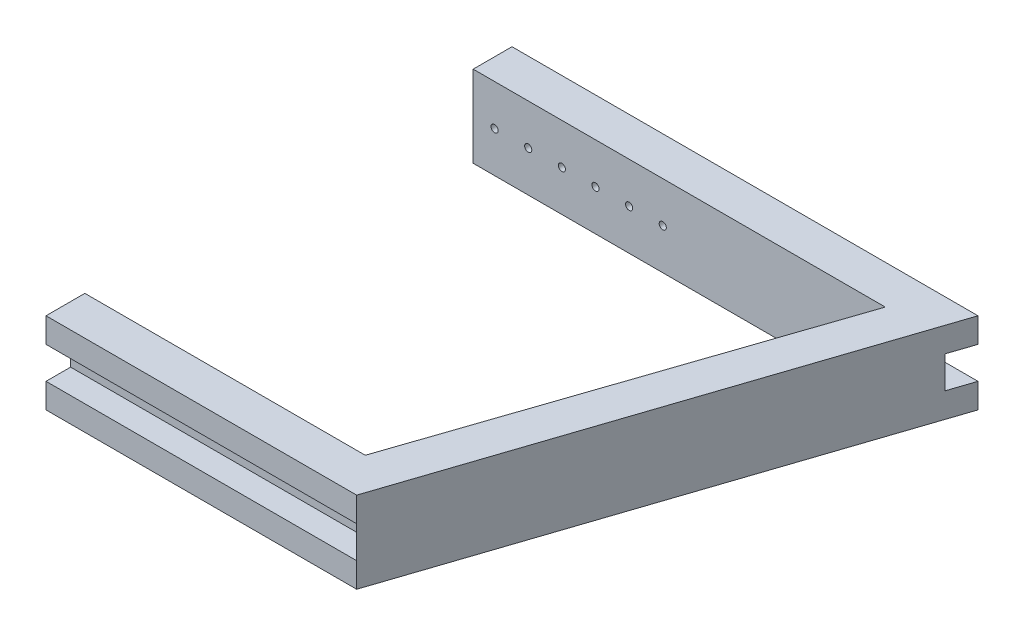
SolidWorks part; units mm, degrees
ref_plane "Front Plane" through (0, 0, 0) normal (0, 0, 1) x (1, 0, 0)
ref_plane "Top Plane" through (0, 0, 0) normal (0, 1, 0) x (1, 0, 0)
ref_plane "Right Plane" through (0, 0, 0) normal (1, 0, 0) x (0, 0, -1)
sketch "Sketch1" plane through (0, 0, 0) normal (0, 1, 0) x (1, 0, 0)
  line L0 (-228.6, 0) -> (228.6, 0)
  line L1 (-228.6, 0) -> (-228.6, -457.2) construction
  line L2 (-228.6, -457.2) -> (76.2, -457.2)
  line L3 (76.2, -457.2) -> (228.6, 0)
  line L4 (-228.6, 0) -> (-228.6, -38.1)
  line L5 (-228.6, -457.2) -> (-228.6, -419.1)
  line L6 (-228.6, -38.1) -> (399.2088, -38.1) construction
  line L7 (-228.6, -419.1) -> (435.0265, -419.1) construction
  line L8 (76.2, -457.2) -> (76.2, 0) construction
  line L9 (84.6667, -431.8) -> (46.5667, -419.1) construction
  line L10 (-228.6, -419.1) -> (46.5667, -419.1)
  line L11 (175.7391, -38.1) -> (46.5667, -419.1)
  line L12 (-228.6, -38.1) -> (175.7391, -38.1)
  line L13 (211.8839, -50.1483) -> (175.7391, -38.1) construction
  point P2 (0, 0)
  point P16 (46.5667, -419.1)
  dimension "D1" = 457.2
  dimension "D2" = 457.2
  dimension "D3" = 304.8
  dimension "D4" = 38.1
  dimension "D5" = 38.1
  dimension "D6" = 38.1
  dimension "D7" = 90
  dimension "D8" = 38.1
  dimension "D9" = 90
extrude "Boss-Extrude1" add sketch "Sketch1" along normal blind 80.0001
sketch "Sketch2" plane through (0, 0, 457.2) normal (0, 0, 1) x (1, 0, 0)
  line L0 (-228.6, 80.0001) -> (-228.6, 0) construction
  line L1 (-228.6, 55.6923) -> (76.2, 55.6923)
  line L2 (-228.6, 55.6923) -> (-228.6, 24.3078)
  line L3 (-228.6, 24.3078) -> (76.2, 24.3078)
  line L4 (76.2, 55.6923) -> (76.2, 24.3078)
  line L5 (76.2, 80.0001) -> (76.2, 0) construction
  point P8 (0, 0)
  point P9 (0, 0)
  point P11 (0, 0)
  point P13 (0, 0)
  dimension "D1" = 24.3078
  dimension "D2" = 24.3078
extrude "Cut-Extrude1" cut sketch "Sketch2" against normal blind 24.12
sketch "Sketch3" plane through (0, 0, 0) normal (0, 0, -1) x (-1, 0, 0)
  line L0 (-228.6, 80.0001) -> (-228.6, 0) construction
  line L1 (-228.6, 55.6923) -> (228.6, 55.6923)
  line L2 (-228.6, 55.6923) -> (-228.6, 24.3078)
  line L3 (-228.6, 24.3078) -> (228.6, 24.3078)
  line L4 (228.6, 55.6923) -> (228.6, 24.3078)
  line L5 (228.6, 80.0001) -> (228.6, 0) construction
  dimension "D1" = 24.3078
  dimension "D2" = 24.3078
extrude "Cut-Extrude2" cut sketch "Sketch3" against normal blind 24.12
sketch "Sketch4" plane through (0, 0, 433.08) normal (0, 0, 1) x (1, 0, 0)
  line L0 (-533.4, 40) -> (76.2, 40) construction
  line L2 (76.2, 24.3078) -> (76.2, 55.6923) construction
  circle A0 centre (-207.6, 40) radius 3.5
  circle A1 centre (-174.6001, 40) radius 3.5
  circle A2 centre (-141.6001, 40) radius 3.5
  circle A3 centre (-108.6002, 40) radius 3.5
  circle A4 centre (-75.6003, 40) radius 3.5
  circle A5 centre (-42.6003, 40) radius 3.5
  point P3 (-228.6, 40)
  point P9 (-179.8736, 31.75)
  point P12 (-147.7945, 31.75)
  point P15 (-115.1895, 31.75)
  point P18 (-82.0586, 31.75)
  point P21 (-47.876, 31.75)
  point P22 (21.2781, 31.75)
  point P23 (-34.7288, 31.75)
  point P24 (-81.5327, 31.75)
  point P25 (-123.3407, 31.75)
  point P26 (-168.0411, 31.75)
  point P27 (0, 0)
  point P28 (0, 0)
  point P29 (-161.7305, 31.75)
  point P30 (-120.4483, 31.75)
  point P31 (0, 0)
  dimension "D1" = 32.9999
  dimension "D2" = 32.9999
  dimension "D3" = 32.9999
  dimension "D4" = 32.9999
  dimension "D5" = 32.9999
  dimension "D6" = 21
extrude "Cut-Extrude3" cut sketch "Sketch4" against normal through all
sketch "Sketch6" plane through (169.2069, 0, 57.3671) normal (-0.9471, 0, -0.3211) x (-0.3211, 0, 0.9471)
  line L0 (381.9572, 80.0001) -> (381.9572, 0) construction
  line L1 (381.9572, 55.6923) -> (-20.3443, 55.6923)
  line L2 (381.9572, 55.6923) -> (381.9572, 24.3078)
  line L3 (381.9572, 24.3078) -> (-20.3443, 24.3078)
  line L4 (-20.3443, 55.6923) -> (-20.3443, 24.3078)
  line L5 (-20.3443, 80.0001) -> (-20.3443, 0) construction
  dimension "D1" = 24.3078
  dimension "D2" = 24.3078
extrude "Cut-Extrude4" cut sketch "Sketch6" against normal blind 24.12
sketch "Sketch7" plane through (169.2069, 0, 57.3671) normal (-0.9471, 0, -0.3211) x (-0.3211, 0, 0.9471)
  line L0 (-20.3443, 80.0001) -> (-20.3443, 55.6923) construction
  line L1 (4.6557, 10.3277) -> (144.8078, 10.3277)
  line L2 (4.6557, 10.3277) -> (4.6557, 69.6877)
  line L3 (4.6557, 69.6877) -> (144.8078, 69.6877)
  line L4 (144.8078, 10.3277) -> (144.8078, 69.6877)
  line L9 (-20.3443, 80.0001) -> (381.9572, 80.0001) construction
  point P6 (0, 0)
  dimension "D1" = 25
  dimension "D2" = 59.36
  dimension "D3" = 10.3124
extrude "Cut-Extrude5" cut sketch "Sketch7" against normal blind 30.48
